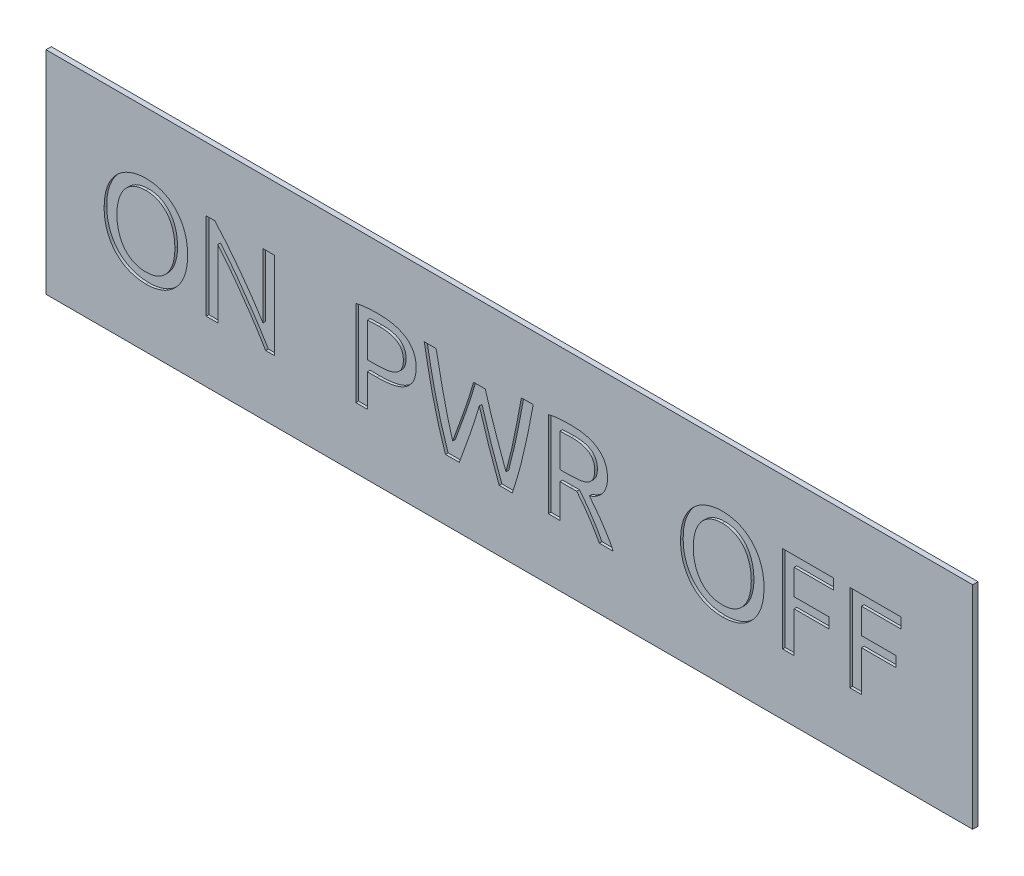
SolidWorks part; units mm, degrees
ref_plane "Front Plane" through (0, 0, 0) normal (0, 0, 1) x (1, 0, 0)
ref_plane "Top Plane" through (0, 0, 0) normal (0, 1, 0) x (1, 0, 0)
ref_plane "Right Plane" through (0, 0, 0) normal (1, 0, 0) x (0, 0, -1)
sketch "Sketch1" plane through (0, 0, 0) normal (0, 0, 1) x (1, 0, 0)
  line L1 (17.5, -4) -> (-17.5, -4)
  line L2 (17.5, -4) -> (17.5, 4)
  line L3 (17.5, 4) -> (-17.5, 4)
  line L4 (-17.5, -4) -> (-17.5, 4)
  line L5 (17.5, -4) -> (-17.5, 4) construction
  line L6 (17.5, 4) -> (-17.5, -4) construction
  point P0 (0, 0)
  dimension "D1" = 8
  dimension "D2" = 35
extrude "Boss-Extrude1" add sketch "Sketch1" along normal mid plane 0.2
sketch "Sketch2" plane through (0, 0, 0.1) normal (0, 0, 1) x (1, 0, 0)
  text T0 "LASER" font "Ubuntu" height in points 12
extrude "Cut-Extrude1" [suppressed] cut sketch "Sketch2" against normal blind 0.1
sketch "Sketch3" plane through (0, 0, 0.1) normal (0, 0, 1) x (1, 0, 0)
  text T0 "MOTOR  X" font "Ubuntu" height in points 12
extrude "Cut-Extrude2" [suppressed] cut sketch "Sketch3" against normal blind 0.1
sketch "Sketch4" [suppressed] plane through (0, 0, 0.1) normal (0, 0, 1) x (1, 0, 0)
  text T0 "MOTOR  Y" font "Ubuntu" height in points 12
extrude "Cut-Extrude3" [suppressed] cut sketch "Sketch4" against normal blind 0.1
sketch "Sketch5" [suppressed] plane through (0, 0, 0.1) normal (0, 0, 1) x (1, 0, 0)
  text T0 "Edge Sensors" font "Ubuntu" height in points 12
extrude "Cut-Extrude4" [suppressed] cut sketch "Sketch5" against normal blind 0.1
sketch "Sketch6" plane through (0, 0, 0.1) normal (0, 0, 1) x (1, 0, 0)
  text T0 "ON  LASER  OFF" font "Ubuntu" height in points 12
extrude "Cut-Extrude5" [suppressed] cut sketch "Sketch6" against normal blind 0.1
sketch "Sketch7" plane through (0, 0, 0.1) normal (0, 0, 1) x (1, 0, 0)
  text T0 "ON  PWR  OFF" font "Ubuntu" height in points 12
extrude "Cut-Extrude6" cut sketch "Sketch7" against normal blind 0.1
